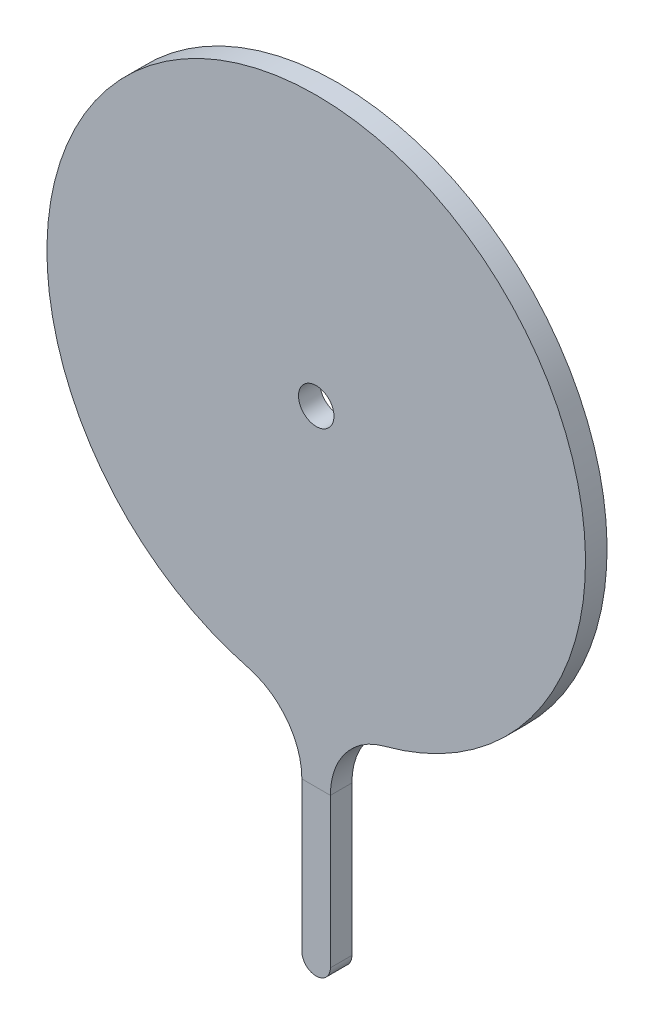
SolidWorks part; units mm, degrees
material "PET"
ref_plane "Front Plane" through (0, 0, 0) normal (0, 0, 1) x (1, 0, 0)
ref_plane "Top Plane" through (0, 0, 0) normal (0, 1, 0) x (1, 0, 0)
ref_plane "Right Plane" through (0, 0, 0) normal (1, 0, 0) x (0, 0, -1)
sketch "Sketch1" plane through (0, 0, 0) normal (0, 0, 1) x (1, 0, 0)
  line L0 (0, -9.525) -> (0, -17.4625) construction
  line L1 (-0.508, -9.5114) -> (-0.508, -17.4625)
  line L2 (0.5, -9.5119) -> (0.5, -17.4625)
  line L4 (-0.508, -17.4625) -> (0.5, -17.4625)
  line L5 (-0.508, -9.525) -> (-0.508, -17.4625) construction
  line L6 (0.5, -9.525) -> (0.5, -17.4625) construction
  arc A1 (0.5, -9.5119) -> (-0.508, -9.5114) centre (0, 0) ccw
  circle A3 centre (0, 0) radius 0.627
  dimension "D2" = 19.05
  dimension "D1" = 1.254
  dimension "D3" = 7.9375
  dimension "D4" = 0.508
  dimension "D5" = 0.5
extrude "Boss-Extrude1" add sketch "Sketch1" along normal blind 0.762
fillet "Fillet1" radius 2.54 2 edges at (0.5, -9.5119, 0.381) (-0.508, -9.5114, 0.381)
fillet "Fillet2" 2 edges at (0.5, -17.4625, 0.381) (-0.508, -17.4625, 0.381) type full round first side face at (0.5, -14.5691, 0.381) second side face at (-0.508, -14.5681, 0.381) middle face at (-0.004, -17.4625, 0.381)
sketch "Sketch2" plane through (0, 0, 0.762) normal (0, 0, 1) x (1, 0, 0)
  line L0 (0.5, -11.6757) -> (-0.508, -11.6736)
split line "Split Line1"
